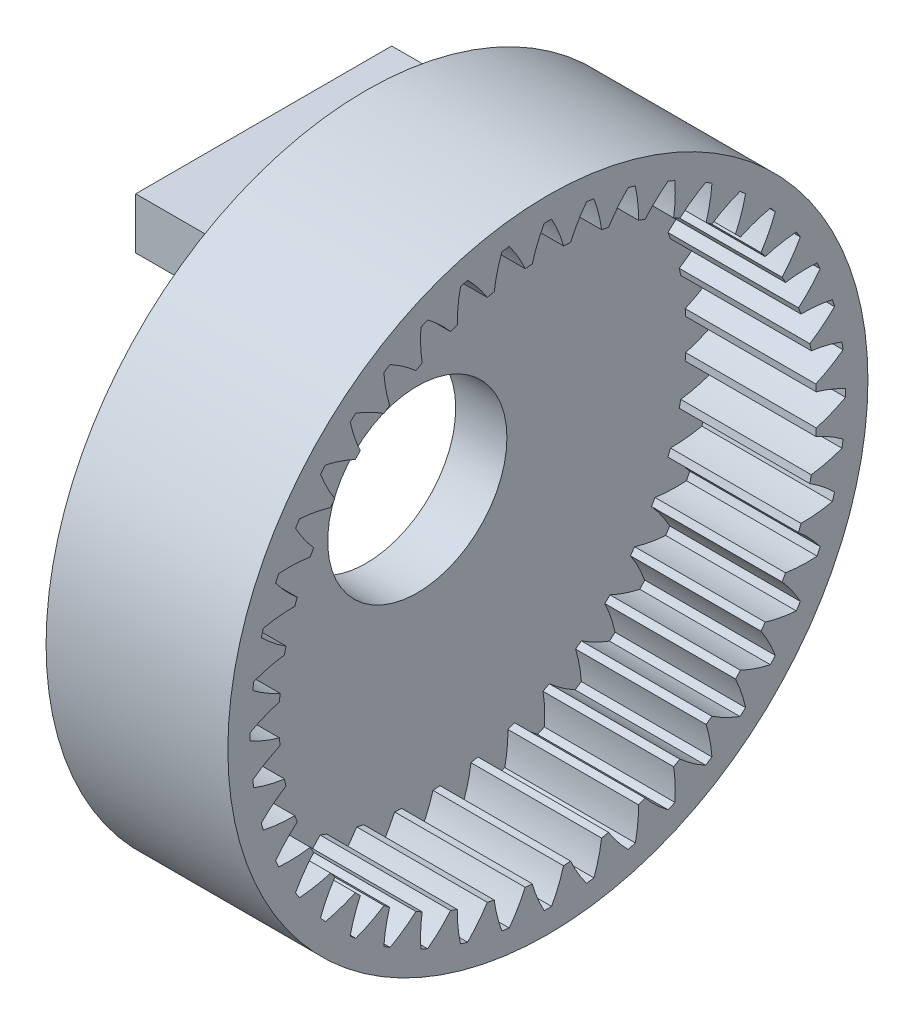
SolidWorks part; units mm, degrees
ref_plane "Plane1" through (0, 0, 0) normal (0, 0, 1) x (1, 0, 0)
ref_plane "Plane2" through (0, 0, 0) normal (0, 1, 0) x (1, 0, 0)
ref_plane "Plane3" through (0, 0, 0) normal (1, 0, 0) x (0, 0, -1)
other "Configuration Table"
sketch "HoldingSke" plane through (0, 0, 0) normal (0, 1, 0) x (1, 0, 0)
  line L0 (0, 0) -> (1.4387, -1.3893)
  line L1 (-15, 0) -> (100, 0) construction
  line L2 (0, 0) -> (-2.1039, 2.3779)
  line L3 (0, 0) -> (-11.863, 4.5341)
  line L4 (0, 0) -> (6.2122, 5.9991)
  line L5 (0, 0) -> (-23.7986, -8.8762)
  line L6 (0, 0) -> (-10.5278, -7.1032)
  line L7 (-2.1039, 2.3779) -> (3.3635, 27.1825)
  line L8 (-76.2, 2.8779) -> (-54.61, 2.8779)
  line L9 (-71.009, 38.7566) -> (-53.1078, 45.2721)
  line L10 (-76.2, 71.12) -> (104.1128, 71.12)
  line L11 (0, 0) -> (-5.1, 0)
  line L12 (-76.2, 101.6) -> (-76.181, 101.6)
  line L13 (24.9733, 27.94) -> (52.9518, 28.4284)
  line L14 (24.9733, 27.94) -> (24.9743, 27.94)
  line L15 (24.9733, 27.94) -> (100.4006, 29.5858)
  circle A0 centre (0, 0) radius 12.5
  circle A1 centre (0, 0) radius 12.7
  circle A2 centre (0, 0) radius 12.7
  dimension "MHD" = 25.4
  dimension "Hub_dia" = 25.4
  dimension "Diameter" = 25
  dimension "Num_teeth" = 44
  dimension "Pitch" = 2
  dimension "Overall_len" = 25.4
  dimension "Show_teeth" = 44
  dimension "Thickness" = 12.7
  dimension "OAL" = 25.4001
  dimension "T_dim" = 21.59
  dimension "Ap" = 20
  dimension "H" = 19.05
  dimension "Pitch_radius" = 180.3128
  dimension "Width" = 5.1
  dimension "Backlash" = 0.019
  dimension "Addendum_fac" = 1
  dimension "Dedendum_fac" = 1.25
  dimension "Clearance_fac" = 0.25
  dimension "Dedendum_add" = 0.001
  dimension "Module" = 0.5
sketch "BasProSke" plane through (0, 0, 0) normal (0, 1, 0) x (1, 0, 0)
  line L0 (-10, 0) -> (60, 0) construction
  line L1 (0, 10.5) -> (0, 12.5)
  line L2 (0, 10.5) -> (5.1, 10.5)
  line L3 (5.1, 10.5) -> (5.1, 12.5)
  line L4 (5.1, 12.5) -> (0, 12.5)
  dimension "Diameter" = 25
  dimension "Thickness" = 5.1
  dimension "Inside_diameter" = 21
revolve "Base-Revolve" add sketch "BasProSke" angle 360 about L0
sketch "TooCutSke" plane through (0, 0, 0) normal (1, 0, 0) x (0, 0, -1)
  line L3 (0.4401, 10.9912) -> (0.4401, 53.6633) construction
  line L4 (0, 0) -> (0, 59.563) construction
  line L5 (0, 0) -> (-4.8744, 68.1534) construction
  line L6 (-4.6836, 8.9917) -> (37.0827, 11.9789) construction
  circle A0 centre (0, 0) radius 11 construction
  circle A1 centre (0, 0) radius 11.626 construction
  circle A2 centre (0, 0) radius 9.303 construction
  circle A3 centre (0, 0) radius 10.4746 construction
  arc A4 (0.6178, 10.4564) -> (0.145, 11.6251) centre (-4.6836, 8.9917) ccw
  arc A5 (0.6178, 10.4564) -> (-0.6178, 10.4564) centre (0, 0) ccw
  arc A6 (0.145, 11.6251) -> (-0.145, 11.6251) centre (0, 0) ccw
  arc A7 (-0.145, 11.6251) -> (-0.6178, 10.4564) centre (4.6836, 8.9917) ccw
  dimension "Pitch_dia" = 22
  dimension "Base_dia" = 18.6059
  dimension "Root_dia" = 23.252
  dimension "Overcut_dia" = 20.9492
  dimension "Flank_rad" = 5.5
  dimension "Half_ang" = 4.091
  dimension "Half_CT" = 0.4401
extrude "ToothCut" cut sketch "TooCutSke" along normal through all
fillet "Breaks" [suppressed] radius 0.05
fillet "RootFillets" [suppressed] radius 0.126
pattern_circular "TeethCuts" count 44 every 8.182 about axis through (-10, 0, 0) along (1, 0, 0) of "RootFillets", "Breaks", "ToothCut"
sketch "草图1" plane through (0, 0, 0) normal (1, 0, 0) x (0, 0, -1)
  line L0 (0, 0) -> (12.5, 0) construction
  line L1 (-5, 9.5) -> (5, 9.5)
  line L2 (-5, 9.5) -> (-5, 7.5)
  line L3 (-5, 7.5) -> (5, 7.5)
  line L4 (5, 9.5) -> (5, 7.5)
  line L5 (0, 0) -> (0, 7.5) construction
  line L6 (-5, -7.5) -> (5, -7.5)
  line L7 (5, -9.5) -> (5, -7.5)
  line L8 (-5, -9.5) -> (5, -9.5)
  line L9 (-5, -9.5) -> (-5, -7.5)
  circle A0 centre (0, 0) radius 7.5
  circle A1 centre (0, 0) radius 3.5
  circle A2 centre (0, 0) radius 12.5
  point P9 (0, 0)
  dimension "D1" = 25
  dimension "D2" = 15
  dimension "D3" = 7
  dimension "D4" = 10
  dimension "D5" = 2
extrude "凸台-拉伸1" add sketch "草图1" against normal blind 2 contours A2 | A1
extrude "凸台-拉伸2" add sketch "草图1<3>" against normal blind 4 from surface contours L4 L1 L2 L3 | L9 L8 L7 L6 region at (0, -8.5, 0) region at (0, 8.5, 0) starting at face at (-2, 0, -3.5)
sketch "草图1<3>" plane through (0, 0, 0) normal (1, 0, 0) x (0, 0, -1) same geometry as "草图1"
equation "' \"Module@HoldingSke\" = 6.35"
equation "' \"Num_teeth@HoldingSke\" = 24"
equation "' \"Ap@HoldingSke\" =  14.5"
equation "' \"Ap@HoldingSke\" = 14.5"
equation "' \"Width@HoldingSke\" = 12"
equation "' \"Diameter@HoldingSke\" = 8 * 25.4"
equation "' \"Show_teeth@HoldingSke\" = 100"
equation "' \"Backlash@HoldingSke\" = 0.009 * 25.4"
equation "' \"Addendum_fac@HoldingSke\" = 1.0"
equation "' \"Dedendum_fac@HoldingSke\" = 1.25"
equation "' \"Dedendum_add@HoldingSke\" = 0.00005 * 25.4"
equation "' \"Clearance_fac@HoldingSke\" = 0.25"
equation "\"Pitch@HoldingSke\" = 1 / \"Module@HoldingSke\" "
equation "\"Overcut_dia@TooCutSke\" = (\"Num_teeth@HoldingSke\" - 2 * \"Addendum_fac@HoldingSke\") / \"Pitch@HoldingSke\" - 0.002 * 25.4"
equation "\"Pitch_dia@TooCutSke\" = \"Num_teeth@HoldingSke\" / \"Pitch@HoldingSke\""
equation "\"Base_dia@TooCutSke\" = \"Num_teeth@HoldingSke\" / \"Pitch@HoldingSke\" * cos((\"Ap@HoldingSke\"  * 3.14159265 / 180)) * 0.90"
equation "\"Root_dia@TooCutSke\" = \"Num_teeth@HoldingSke\"  / \"Pitch@HoldingSke\" + 2 *  \"Dedendum_fac@HoldingSke\"/ \"Pitch@HoldingSke\" + \"Dedendum_add@HoldingSke\" * 2"
equation "\"Half_ang@TooCutSke\" = 180 / \"Num_teeth@HoldingSke\""
equation "\"Half_CT@TooCutSke\" = \"Num_teeth@HoldingSke\" / \"Pitch@HoldingSke\" * sin((3.14159265 / 2 / \"Num_teeth@HoldingSke\")) / 2 + 10 * \"Backlash@HoldingSke\" / 4"
equation "\"Flank_rad@TooCutSke\" = \"Num_teeth@HoldingSke\" / \"Pitch@HoldingSke\" / 4"
equation "\"Radius@RootFillets\"= \"Clearance_fac@HoldingSke\" / \"Pitch@HoldingSke\" + \"Dedendum_add@HoldingSke\""
equation "\"Break_rad@Breaks\" = 0.02 / \"Pitch@HoldingSke\" * 5"
equation "\"Num_teeth@TeethCuts\" = int( \"Show_teeth@HoldingSke\" ) + 1"
equation "\"Num_teeth@TeethCuts\" = ((sgn( \"Num_teeth@TeethCuts\" - \"Num_teeth@HoldingSke\" )-1)*( \"Num_teeth@TeethCuts\" - \"Num_teeth@HoldingSke\" ))/-2+ \"Num_teeth@HoldingSke\""
equation "\"Num_teeth@TeethCuts\" = ((sgn( \"Num_teeth@TeethCuts\" - 2.0)+1)*( \"Num_teeth@TeethCuts\" - 2.0))/2 +2.0"
equation "\"Angle@TeethCuts\" = 360.0 / \"Num_teeth@HoldingSke\""
equation "\"Diameter@BasProSke\" = \"Num_teeth@HoldingSke\"  / \"Pitch@HoldingSke\" + 2 *  \"Dedendum_fac@HoldingSke\"/ \"Pitch@HoldingSke\" + \"Dedendum_add@HoldingSke\" * 2 + 0.002 * 25.4"
equation "\"Diameter@BasProSke\" = ((sgn( \"Diameter@BasProSke\"  - \"Diameter@HoldingSke\" )+1)*( \"Diameter@BasProSke\"  - \"Diameter@HoldingSke\" ))/2 + \"Diameter@HoldingSke\""
equation "\"Inside_diameter@BasProSke\" =  (\"Num_teeth@HoldingSke\" - 2 * \"Addendum_fac@HoldingSke\") / \"Pitch@HoldingSke\" "
equation "\"Thickness@BasProSke\"  = \"Width@HoldingSke\""
